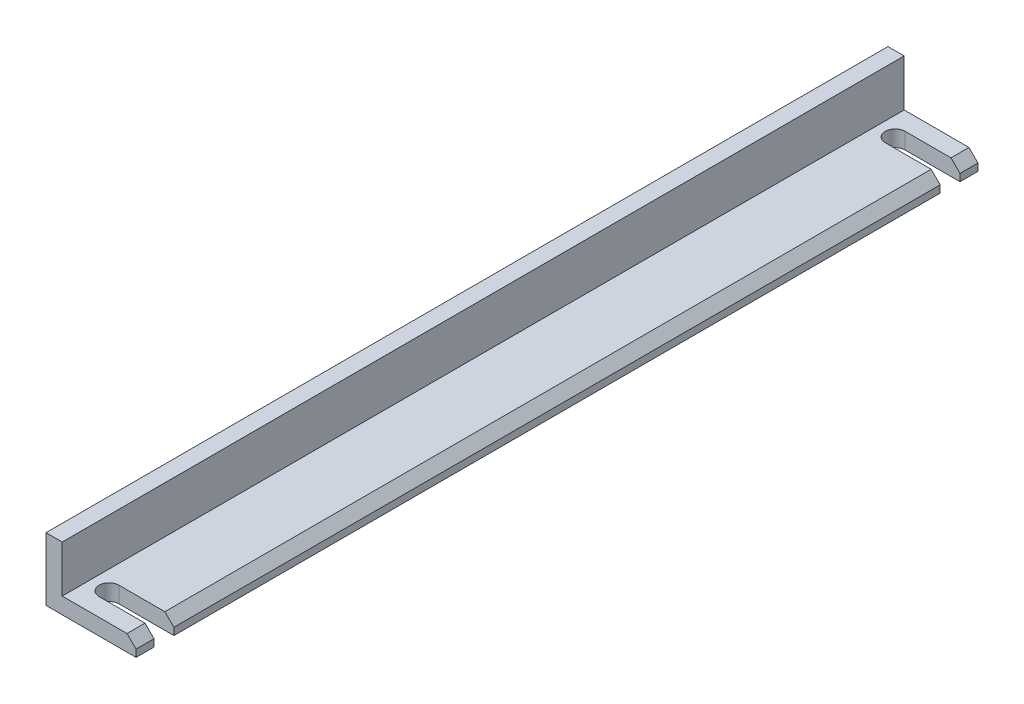
SolidWorks part; units mm, degrees
material "AISI 316 Stainless Steel Sheet (SS)"
ref_plane "Спереди" through (0, 0, 0) normal (0, 0, 1) x (1, 0, 0)
ref_plane "Сверху" through (0, 0, 0) normal (0, 1, 0) x (1, 0, 0)
ref_plane "Справа" through (0, 0, 0) normal (1, 0, 0) x (0, 0, -1)
sketch "Sketch1" plane through (0, 0, 0) normal (0, 0, 1) x (1, 0, 0)
  line L0 (0, 0) -> (0, 7)
  line L1 (0, 0) -> (10, 0)
  dimension "D1" = 10
  dimension "D2" = 7
extrude "Extrude-Thin1" add sketch "Sketch1" along normal mid plane 93.5 thin thin type one direction reverse wall 1.8
chamfer "Chamfer1" distance 1 angle 45 1 edges at (10, 1.8, 0)
sketch "Sketch2" plane through (0, 1.8, 0) normal (0, 1, 0) x (1, 0, 0)
  line L0 (11.5225, -43.65) -> (3.9, -43.65) construction
  line L1 (11.5225, -44.75) -> (3.9, -44.75)
  line L2 (11.5225, -42.55) -> (3.9, -42.55)
  line L3 (1.8, -46.75) -> (9, -46.75) construction
  line L4 (1.8, -46.75) -> (1.8, 46.75) construction
  arc A0 (11.5225, -44.75) -> (11.5225, -42.55) centre (11.5225, -43.65) ccw
  arc A1 (3.9, -42.55) -> (3.9, -44.75) centre (3.9, -43.65) ccw
  point P2 (7.7113, -43.65)
  dimension "D3" = 1
  dimension "D1" = 2.2
  dimension "D2" = 2
extrude "Cut-Extrude1" cut sketch "Sketch2" against normal blind 10
mirror "Mirror1" about plane through (0, 0, 0) normal (0, 0, 1) of "Cut-Extrude1"
